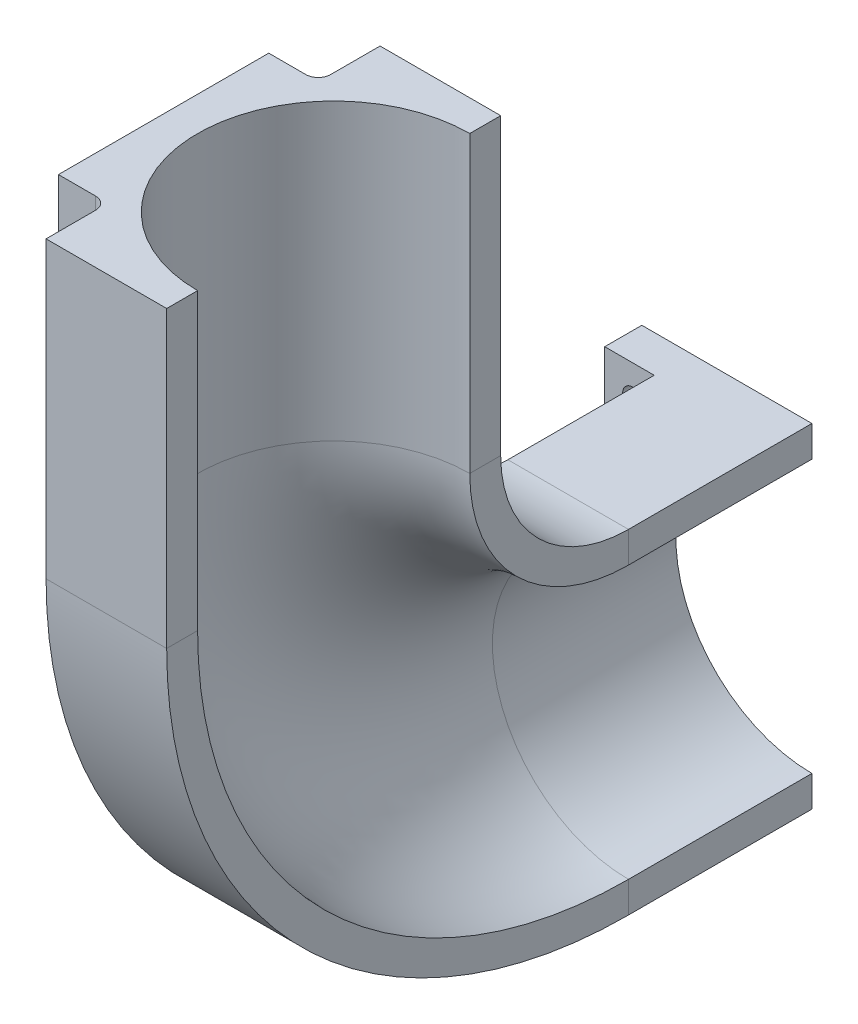
SolidWorks part; units mm, degrees
ref_plane "Front" through (0, 0, 0) normal (0, 0, 1) x (1, 0, 0)
ref_plane "Top" through (0, 0, 0) normal (0, 1, 0) x (1, 0, 0)
ref_plane "Right" through (0, 0, 0) normal (1, 0, 0) x (0, 0, -1)
sketch "草图1" plane through (0, 0, 0) normal (0, 0, 1) x (1, 0, 0)
  line L0 (0, 0) -> (27.5, 0)
  line L1 (0, 0) -> (0, -54)
  line L2 (0, -54) -> (27.5, -54)
  line L3 (27.5, -54) -> (27.5, -49)
  line L4 (27.5, 0) -> (27.5, -5)
  arc A0 (27.5, -5) -> (27.5, -49) centre (27.5, -27) ccw
  point P9 (27.5, -43.4465)
  point P10 (27.5, 0)
  point P11 (27.5, 0)
  point P12 (31.1616, -29.2639)
  point P13 (0, 0)
  point P14 (0, -27)
  point P15 (0, 0)
  point P16 (0, 0)
  dimension "D3" = 44
  dimension "D1" = 54
  dimension "D2" = 27.5
extrude "凸台-拉伸1" add sketch "草图1" along normal blind 6
sketch "草图2" plane through (0, 0, 6) normal (0, 0, 1) x (1, 0, 0)
  line L0 (8, 0) -> (8, -8)
  line L1 (6, -10) -> (0, -10)
  line L2 (8, -46) -> (8, -54)
  line L3 (6, -44) -> (0, -44)
  line L5 (0, 0) -> (0, -54)
  line L6 (0, -54) -> (27.5, -54)
  line L7 (27.5, -54) -> (27.5, -49)
  line L8 (27.5, -5) -> (27.5, 0)
  line L9 (27.5, 0) -> (0, 0)
  line L10 (0, -10) -> (0, -44)
  line L11 (8, -54) -> (27.5, -54)
  line L12 (27.5, -54) -> (27.5, -49)
  line L13 (27.5, -5) -> (27.5, 0)
  line L14 (27.5, 0) -> (8, 0)
  arc A0 (8, -46) -> (6, -44) centre (6, -46) ccw
  arc A1 (27.5, -5) -> (27.5, -49) centre (27.5, -27) ccw
  arc A2 (27.5, -5) -> (27.5, -49) centre (27.5, -27) ccw
  arc A3 (8, -8) -> (6, -10) centre (6, -8) cw
  point P17 (8, -10)
  dimension "D4" = 2
  dimension "D2" = 10
  dimension "D3" = 8
  dimension "D1" = 0
sketch "草图3" plane through (27.5, 0, 0) normal (1, 0, 0) x (0, 0, -1)
  line L0 (-6, -27) -> (-29.66, -27)
  line L1 (-6, -10) -> (-6, -44) construction
  line L2 (-77.32, 20.66) -> (-77.32, 68.26)
  arc A0 (-29.66, -27) -> (-77.32, 20.66) centre (-29.66, 20.66) cw
  dimension "D2" = 47.66
  dimension "D1" = 23.66
  dimension "D3" = 47.6
sweep "扫描1" add profiles "草图2" path "草图3"
sketch "草图4" plane through (0, 0, 6) normal (0, 0, 1) x (1, 0, 0)
  line L0 (0, 0) -> (0, -10) construction
  line L1 (8, 0) -> (0, 0) construction
  circle A0 centre (4.5, -5) radius 1.6
  dimension "D1" = 3.2
  dimension "D2" = 4.5
  dimension "D3" = 5
extrude "切除-拉伸1" cut sketch "草图4" against normal through all contours A0
ref_plane "基准面2" through (0, -27, 0) normal (0, 1, 0) x (1, 0, 0)
mirror "镜向1" about plane through (0, -27, 0) normal (0, 1, 0) of "切除-拉伸1"
